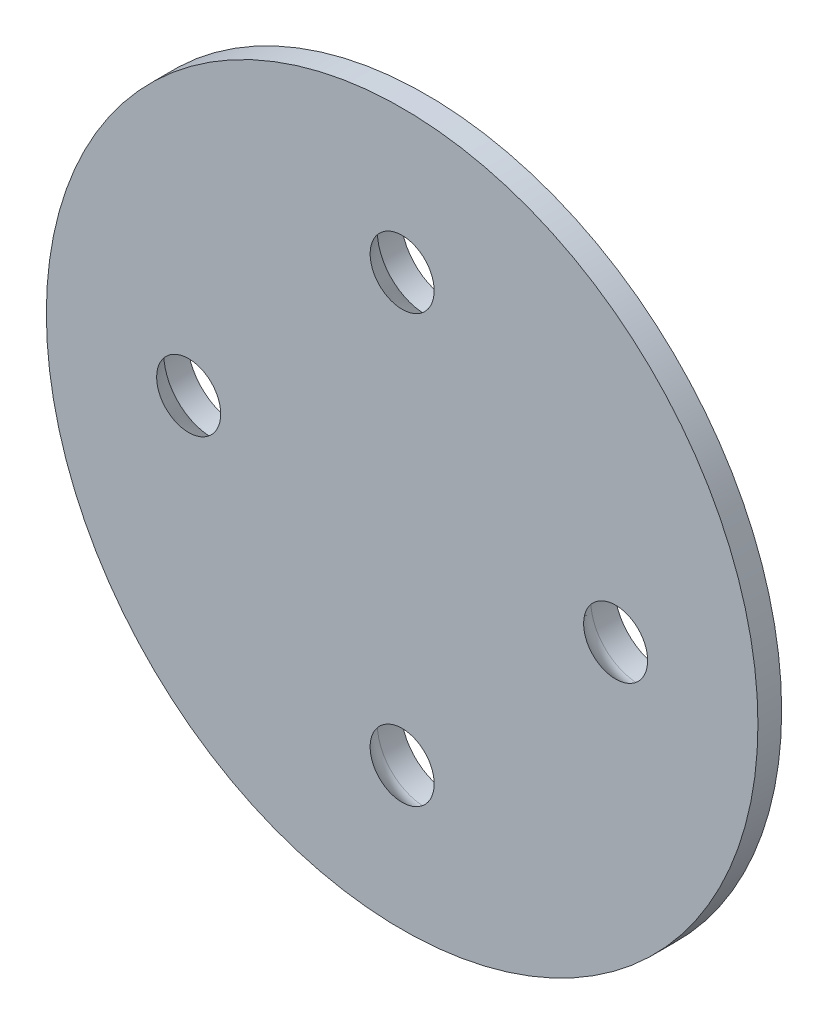
SolidWorks part; units mm, degrees
material "ABS"
ref_plane "正面" through (0, 0, 0) normal (0, 0, 1) x (1, 0, 0)
ref_plane "平面" through (0, 0, 0) normal (0, 1, 0) x (1, 0, 0)
ref_plane "右側面" through (0, 0, 0) normal (1, 0, 0) x (0, 0, -1)
sketch "ｽｹｯﾁ1" plane through (0, 0, 0) normal (0, 0, 1) x (1, 0, 0)
  circle A0 centre (0, 0) radius 15
  dimension "D1" = 30
extrude "ﾎﾞｽ - 押し出し1" add sketch "ｽｹｯﾁ1" along normal blind 1
sketch "ｽｹｯﾁ2" plane through (0, 0, 0) normal (0, 0, -1) x (-1, 0, 0)
  circle A0 centre (0, 0) radius 13
  dimension "D1" = 26
extrude "ﾎﾞｽ - 押し出し2" add sketch "ｽｹｯﾁ2" along normal blind 1
sketch "ｽｹｯﾁ3" plane through (0, 0, -1) normal (0, 0, -1) x (-1, 0, 0)
  circle A0 centre (9, 0) radius 2.05
  circle A1 centre (0, -9) radius 2.05
  circle A2 centre (-9, 0) radius 2.05
  circle A3 centre (0, 9) radius 2.05
  point P2 (-6.95, 0)
  point P4 (-9.6307, -17.1827)
  point P5 (0, -6.95)
  point P12 (0, 0)
  point P13 (6.95, 0)
  point P14 (0, 6.95)
  dimension "D1" = 4.1
  dimension "D2" = 9
  dimension "D3" = 4
extrude "ｶｯﾄ - 押し出し1" cut sketch "ｽｹｯﾁ3" against normal blind 1
sketch "ｽｹｯﾁ4" plane through (0, 0, 1) normal (0, 0, 1) x (1, 0, 0)
  circle A0 centre (-9, 0) radius 1.35
  circle A1 centre (0, 9) radius 1.35
  circle A2 centre (9, 0) radius 1.35
  circle A3 centre (0, -9) radius 1.35
  point P2 (7.65, 0)
  point P4 (16.8354, 18.714)
  point P5 (0, 7.65)
  point P12 (0, 0)
  point P13 (-7.65, 0)
  point P14 (0, -7.65)
  dimension "D1" = 2.7
  dimension "D2" = 9
  dimension "D3" = 4
loft "ｶｯﾄ - ﾛﾌﾄ2" cut section edge at (6.95, 0, 0) section "ｽｹｯﾁ4" start constraint normal to profile start tangent length 1 connector at (6.9624, -0.2248, 0) connector at (7.65, 0.0079, 1)
sketch "ｽｹｯﾁ5" plane through (0, 0, 1) normal (0, 0, 1) x (1, 0, 0)
  line L0 (0, 0) -> (9, 0) construction
  point P3 (9, 0)
loft "ｶｯﾄ - ﾛﾌﾄ3" cut section edge at (-2.05, -9, 0) section "ｽｹｯﾁ4<5>" start constraint normal to profile start tangent length 1 connector at (-0.0223, -6.9501, 0) connector at (-0.0219, -7.6502, 1)
sketch "ｽｹｯﾁ4<5>" plane through (0, 0, 1) normal (0, 0, 1) x (1, 0, 0) same geometry as "ｽｹｯﾁ4"
loft "ｶｯﾄ - ﾛﾌﾄ5" cut section edge at (-11.05, 0, 0) section "ｽｹｯﾁ4<6>" connector at (-6.95, -0.0077, 0) connector at (-7.6501, -0.0142, 1)
sketch "ｽｹｯﾁ4<6>" plane through (0, 0, 1) normal (0, 0, 1) x (1, 0, 0) same geometry as "ｽｹｯﾁ4"
loft "ｶｯﾄ - ﾛﾌﾄ6" cut section edge at (-2.05, 9, 0) section "ｽｹｯﾁ4<7>" connector at (-0.0237, 6.9501, 0) connector at (-0.0238, 7.6502, 1)
sketch "ｽｹｯﾁ4<7>" plane through (0, 0, 1) normal (0, 0, 1) x (1, 0, 0) same geometry as "ｽｹｯﾁ4"
